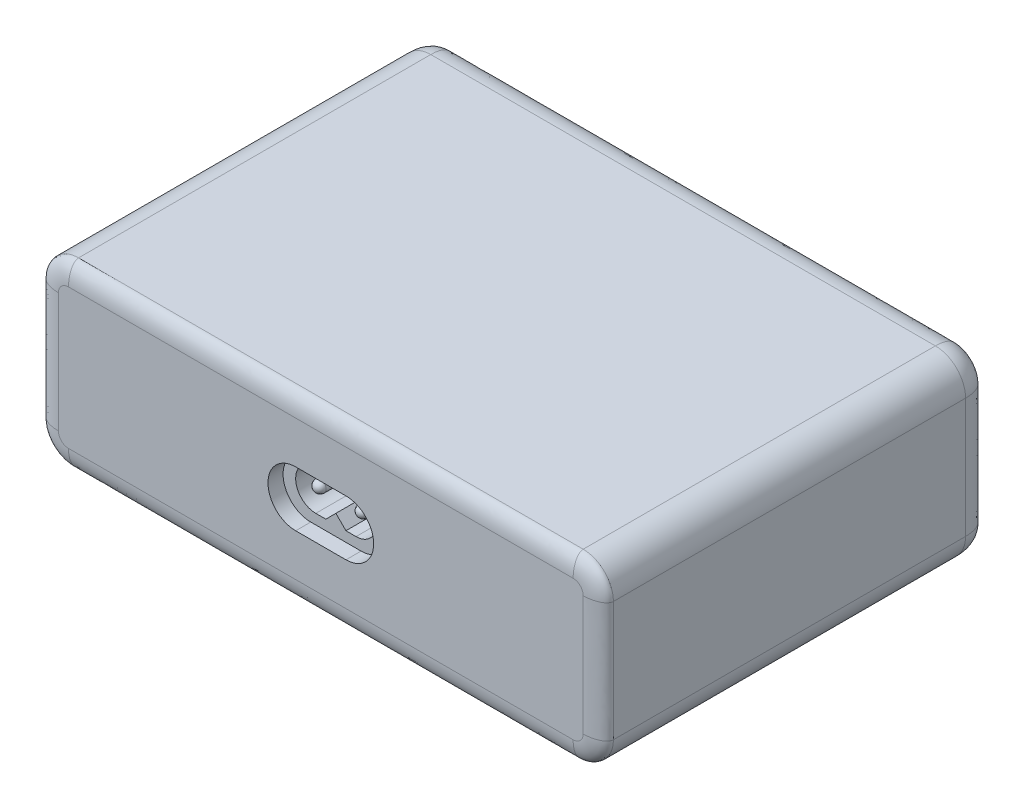
SolidWorks part; units mm, degrees
ref_plane "Front Plane" through (0, 0, 0) normal (0, 0, 1) x (1, 0, 0)
ref_plane "Top Plane" through (0, 0, 0) normal (0, 1, 0) x (1, 0, 0)
ref_plane "Right Plane" through (0, 0, 0) normal (1, 0, 0) x (0, 0, -1)
sketch "Sketch1" plane through (0, 0, 0) normal (0, 1, 0) x (1, 0, 0)
  line L1 (0, 0) -> (112.3, 0)
  line L2 (0, 0) -> (0, 76)
  line L3 (0, 76) -> (112.3, 76)
  line L4 (112.3, 0) -> (112.3, 76)
  dimension "D1" = 76
  dimension "D2" = 112.3
extrude "Boss-Extrude1" add sketch "Sketch1" along normal blind 35.8
fillet "Fillet1" radius 6 4 edges at (0, 35.8, -38) (0, 0, -38) (112.3, 0, -38) (112.3, 35.8, -38)
sketch "Sketch2" plane through (0, 0, 0) normal (0, 0, 1) x (1, 0, 0)
  line L0 (56.15, 35.8) -> (56.15, 0) construction
  line L1 (6, 35.8) -> (106.3, 35.8) construction
  line L2 (6, 0) -> (106.3, 0) construction
  line L3 (51.15, 17.9) -> (61.15, 17.9) construction
  line L4 (51.15, 23.4) -> (61.15, 23.4)
  line L5 (51.15, 12.4) -> (61.15, 12.4)
  arc A0 (51.15, 23.4) -> (51.15, 12.4) centre (51.15, 17.9) ccw
  arc A1 (61.15, 12.4) -> (61.15, 23.4) centre (61.15, 17.9) ccw
  point P8 (56.15, 17.9)
  dimension "D1" = 11
  dimension "D2" = 10
extrude "Cut-Extrude1" cut sketch "Sketch2" against normal blind 3
sketch "Sketch3" plane through (0, 0, -3) normal (0, 0, 1) x (1, 0, 0)
  line L0 (56.15, 23.4) -> (56.15, 12.4) construction
  line L1 (61.15, 23.4) -> (51.15, 23.4) construction
  line L2 (51.15, 12.4) -> (61.15, 12.4) construction
  line L3 (52.15, 18.4) -> (60.15, 18.4) construction
  line L4 (52.15, 22.4) -> (60.15, 22.4)
  line L5 (52.15, 14.4) -> (60.15, 14.4)
  line L6 (48.15, 18.4) -> (64.15, 18.4) construction
  line L7 (61.15, 23.4) -> (51.15, 23.4) construction
  line L8 (54.15, 22.4) -> (56.15, 20.406)
  line L9 (56.15, 20.406) -> (58.15, 22.4)
  line L10 (54.162, 14.4) -> (56.15, 16.406)
  line L11 (56.15, 16.406) -> (58.138, 14.4)
  arc A0 (52.15, 22.4) -> (52.15, 14.4) centre (52.15, 18.4) ccw
  arc A1 (60.15, 14.4) -> (60.15, 22.4) centre (60.15, 18.4) ccw
  point P8 (56.15, 18.4)
  dimension "D1" = 8
  dimension "D2" = 16
  dimension "D3" = 1
  dimension "D4" = 4
  dimension "D5" = 4
extrude "Cut-Extrude2" cut sketch "Sketch3" against normal blind 9.8 contours L5 A1 L4 L9 L8 A0 L10 L11
sketch "Sketch4" plane through (0, 0, -12.8) normal (0, 0, 1) x (1, 0, 0)
  line L0 (56.15, 20.406) -> (56.15, 16.406) construction
  line L1 (56.15, 18.406) -> (51.85, 18.406) construction
  line L2 (56.15, 18.406) -> (60.45, 18.406) construction
  circle A0 centre (51.85, 18.406) radius 1.18
  circle A1 centre (60.45, 18.406) radius 1.18
  dimension "D2" = 2.36
  dimension "D1" = 8.6
extrude "Boss-Extrude2" add sketch "Sketch4" along normal blind 9.8
fillet "Fillet2" radius 1.18 2 edges at (61.63, 18.406, -3) (53.03, 18.406, -3)
fillet "Fillet3" radius 2 16 edges at (56.15, 0, 0) (1.7574, 1.7574, 0) (110.5426, 1.7574, 0) (0, 17.9, 0) (112.3, 17.9, 0) (1.7574, 34.0426, 0) (110.5426, 34.0426, 0) (56.15, 35.8, 0) (56.15, 0, -76) (110.5426, 1.7574, -76) (1.7574, 1.7574, -76) (112.3, 17.9, -76) (0, 17.9, -76) (110.5426, 34.0426, -76) (1.7574, 34.0426, -76) (56.15, 35.8, -76)
sketch "Sketch5" plane through (0, 0, -76) normal (0, 0, -1) x (-1, 0, 0)
  line L0 (-110.3, 16.4267) -> (-100.3, 16.4267) construction
  line L1 (-100.3, 18.8) -> (-87.9, 18.8)
  line L2 (-100.3, 18.8) -> (-100.3, 14)
  line L3 (-100.3, 14) -> (-87.9, 14)
  line L4 (-87.9, 18.8) -> (-87.9, 14)
  line L5 (-81.9, 18.8) -> (-69.5, 18.8)
  line L6 (-81.9, 18.8) -> (-81.9, 14)
  line L7 (-81.9, 14) -> (-69.5, 14)
  line L8 (-69.5, 18.8) -> (-69.5, 14)
  line L9 (-110.3, 29.8) -> (-110.3, 6) construction
  line L10 (-100.3, 16.4267) -> (-87.9, 16.4267) construction
  line L11 (-87.9, 16.4267) -> (-81.9, 16.4267) construction
  line L12 (-81.9, 16.4267) -> (-69.5, 16.4267) construction
  line L13 (-6, 0) -> (-106.3, 0) construction
  line L14 (-112.3, 6) -> (-112.3, 29.8) construction
  dimension "D1" = 14
  dimension "D2" = 12
  dimension "D3" = 12.4
  dimension "D4" = 6
  dimension "D5" = 4.8
extrude "Cut-Extrude3" cut sketch "Sketch5" against normal blind 10.7
sketch "Sketch6" plane through (0, 0, -76) normal (0, 0, -1) x (-1, 0, 0)
  line L0 (-69.5, 16.4) -> (-17.6, 16.4) construction
  line L1 (-69.5, 14) -> (-69.5, 18.8) construction
  line L2 (-21.1, 16.4) -> (-14.1, 16.4) construction
  line L3 (-21.1, 17.7) -> (-14.1, 17.7)
  line L4 (-21.1, 15.1) -> (-14.1, 15.1)
  line L5 (-12.8, 16.4) -> (0, 16.4) construction
  line L6 (0, 29.8) -> (0, 6) construction
  arc A0 (-21.1, 17.7) -> (-21.1, 15.1) centre (-21.1, 16.4) ccw
  arc A1 (-14.1, 15.1) -> (-14.1, 17.7) centre (-14.1, 16.4) ccw
  point P6 (-17.6, 16.4)
  dimension "D1" = 2.6
  dimension "D2" = 7
  dimension "D3" = 12.8
extrude "Cut-Extrude4" cut sketch "Sketch6" against normal blind 8
pattern_linear "LPattern1" count 4 spacing 12.8 along (1, 0, 0) of "Cut-Extrude4"
